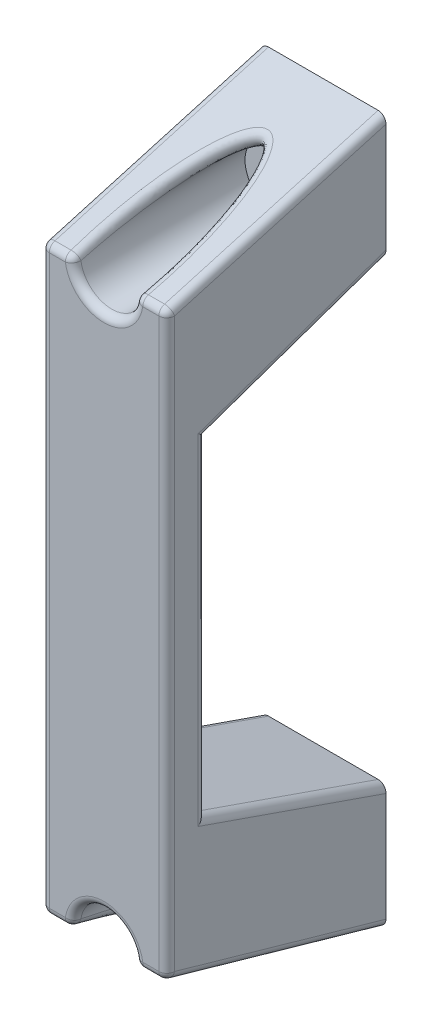
SolidWorks part; units mm, degrees
ref_plane "Front Plane" through (0, 0, 0) normal (0, 0, 1) x (1, 0, 0)
ref_plane "Top Plane" through (0, 0, 0) normal (0, 1, 0) x (1, 0, 0)
ref_plane "Right Plane" through (0, 0, 0) normal (1, 0, 0) x (0, 0, -1)
sketch "Sketch1" plane through (0, 0, 0) normal (0, 0, 1) x (1, 0, 0)
  line L1 (0, 0) -> (16, 0)
  line L2 (0, 0) -> (0, 90)
  line L3 (0, 90) -> (16, 90)
  line L4 (16, 0) -> (16, 90)
  circle A0 centre (8, 82) radius 2.2
  circle A1 centre (8, 8) radius 2.2
extrude "Boss-Extrude1" add sketch "Sketch1" along normal blind 28
sketch "Sketch2" plane through (16, 0, 0) normal (1, 0, 0) x (0, 0, -1)
  line L1 (0, 0) -> (0, 90) construction
  line L7 (-28, 82) -> (-28, 90)
  line L8 (-28, 0) -> (-28, 8)
  line L9 (-28, 0) -> (0, 0)
  line L10 (-28, 8) -> (0, 0)
  line L11 (-28, 82) -> (0, 90)
  line L12 (-28, 90) -> (0, 90)
  line L13 (0, 16) -> (-23, 24)
  line L14 (-23, 24) -> (-23, 66)
  line L15 (-23, 66) -> (0, 74)
  line L16 (0, 16) -> (0, 74)
extrude "Cut-Extrude1" cut sketch "Sketch2" against normal up to surface (16 mm away) up to face at (0, 45, 14)
sketch "Sketch3" plane through (0, 0, 28) normal (0, 0, 1) x (1, 0, 0)
  circle A0 centre (8, 82) radius 4
  circle A1 centre (8, 8) radius 4
extrude "Cut-Extrude2" cut sketch "Sketch3" against normal offset from surface (22 mm away) 6 up to face at (8, 82, 0)
fillet "Fillet1" radius 1 20 edges at (16, 4, 14) (16, 20, 11.5) (16, 45, 23) (16, 70, 11.5) (16, 86, 14) (0, 86, 14) (0, 70, 11.5) (0, 45, 23) (0, 20, 11.5) (0, 4, 14) (2, 8, 28) (14, 8, 28) (16, 45, 28) (0, 45, 28) (2, 82, 28) (14, 82, 28) (8, 78, 28) (8, 12, 28) (8, 4, 14) (8, 86, 14)
